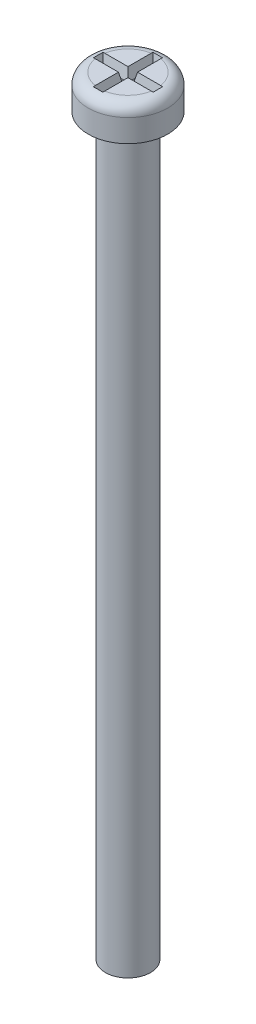
SolidWorks part; units mm, degrees
ref_plane "Спереди" through (0, 0, 0) normal (0, 0, 1) x (1, 0, 0)
ref_plane "Сверху" through (0, 0, 0) normal (0, 1, 0) x (1, 0, 0)
ref_plane "Справа" through (0, 0, 0) normal (1, 0, 0) x (0, 0, -1)
sketch "Эскиз1" plane through (0, 0, 0) normal (0, 1, 0) x (1, 0, 0)
  circle A0 centre (0, 0) radius 2
extrude "Бобышка-Вытянуть1" add sketch "Эскиз1" along normal blind 65
sketch "Эскиз2" plane through (0, 65, 0) normal (0, 1, 0) x (1, 0, 0)
  circle A0 centre (0, 0) radius 3.515
extrude "Бобышка-Вытянуть2" add sketch "Эскиз2" along normal blind 3
sketch "Эскиз3" plane through (0, 68, 0) normal (0, 1, 0) x (1, 0, 0)
  line L0 (-2.6415, 0.4228) -> (-0.4228, 0.4228)
  line L2 (-2.6415, -0.4228) -> (-2.6415, 0.4228)
  line L4 (2.6415, -0.4228) -> (2.6415, 0.4228)
  line L5 (-2.6415, -0.4228) -> (2.6415, 0.4228) construction
  line L6 (-2.6415, 0.4228) -> (2.6415, -0.4228) construction
  line L7 (-0.4228, -2.6415) -> (0.4228, -2.6415)
  line L9 (-0.4228, 2.6415) -> (0.4228, 2.6415)
  line L11 (-0.4228, -2.6415) -> (0.4228, 2.6415) construction
  line L12 (-0.4228, 2.6415) -> (0.4228, -2.6415) construction
  line L13 (-0.4228, 0.4228) -> (-0.4228, 2.6415)
  line L14 (0.4228, 2.6415) -> (0.4228, 0.4228)
  line L15 (0.4228, 0.4228) -> (2.6415, 0.4228)
  line L16 (2.6415, -0.4228) -> (0.4228, -0.4228)
  line L17 (0.4228, -0.4228) -> (0.4228, -2.6415)
  line L18 (-0.4228, -2.6415) -> (-0.4228, -0.4228)
  line L19 (-0.4228, -0.4228) -> (-2.6415, -0.4228)
  point P0 (0, 0)
  point P6 (0, 0)
extrude "Вырез-Вытянуть1" cut sketch "Эскиз3" against normal blind 1 draft 12
fillet "Скругление2" radius 1 1 edges at (0, 68, 3.515)
